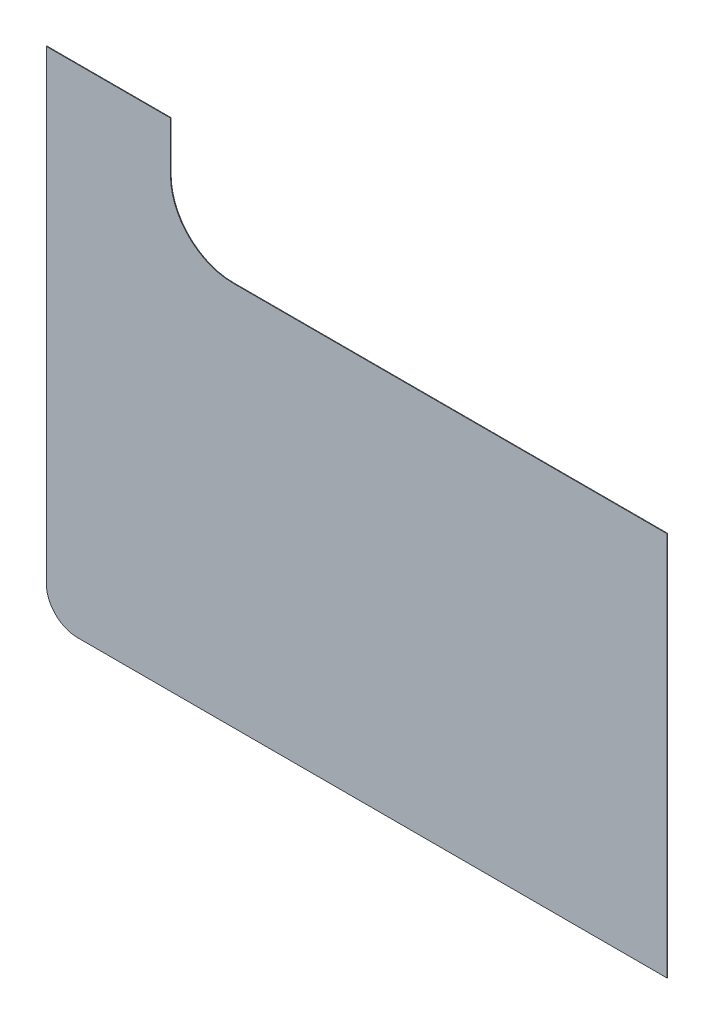
SolidWorks part; units mm, degrees
ref_plane "前视基准面" through (0, 0, 0) normal (0, 0, 1) x (1, 0, 0)
ref_plane "上视基准面" through (0, 0, 0) normal (0, 1, 0) x (1, 0, 0)
ref_plane "右视基准面" through (0, 0, 0) normal (1, 0, 0) x (0, 0, -1)
sketch "草图1" plane through (0, 0, 0) normal (0, 0, 1) x (1, 0, 0)
  line L0 (0, 0) -> (-100, 0)
  line L1 (-100, 0) -> (-100, 80)
  line L2 (-100, 80) -> (-80, 80)
  line L3 (-80, 80) -> (-80, 62)
  line L4 (-80, 62) -> (0, 62)
  line L5 (0, 62) -> (0, 0)
  dimension "D1" = 80
  dimension "D2" = 100
  dimension "D3" = 20
  dimension "D4" = 62
extrude "凸台-拉伸1" add sketch "草图1" along normal blind 0.1
fillet "圆角1" radius 10 1 edges at (-80, 62, 0.05)
fillet "圆角2" radius 5 1 edges at (-100, 0, 0.05)
sketch3d "3D草图1" [suppressed]
  line L0 (-11.5, 30, 0.5) -> (-11.5, 100, 0.5) construction
  arc A0 (-1.5, 20, 0.5) -> (-11.5, 30, 0.5) centre (-1.5, 30, 0.5) ccw construction
  point P0 (-1.5, 20, 0.5)
  point P1 (-8.5711, 22.9289, 0.5)
  point P3 (-11.5, 30, 0.5)
  point P7 (-1.5, 30, -9.5)
  point P8 (-11.5, 49.1552, 0.5)
  point P10 (-11.5, 87.2694, 0.5)
